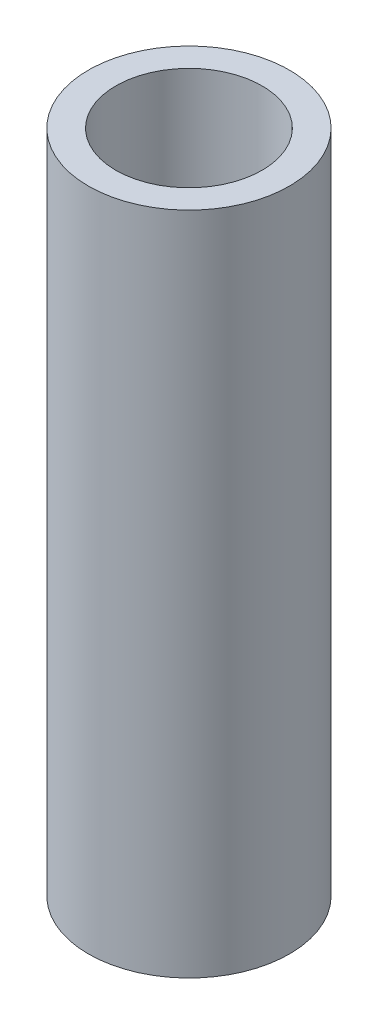
SolidWorks part; units mm, degrees
ref_plane "Front Plane" through (0, 0, 0) normal (0, 0, 1) x (1, 0, 0)
ref_plane "Top Plane" through (0, 0, 0) normal (0, 1, 0) x (1, 0, 0)
ref_plane "Right Plane" through (0, 0, 0) normal (1, 0, 0) x (0, 0, -1)
sketch "Sketch1" plane through (0, 0, 0) normal (0, 1, 0) x (1, 0, 0)
  circle A0 centre (0, 0) radius 24.3078
  circle A1 centre (0, 0) radius 33.401
extrude "Boss-Extrude1" add sketch "Sketch1" along normal mid plane 220.98
